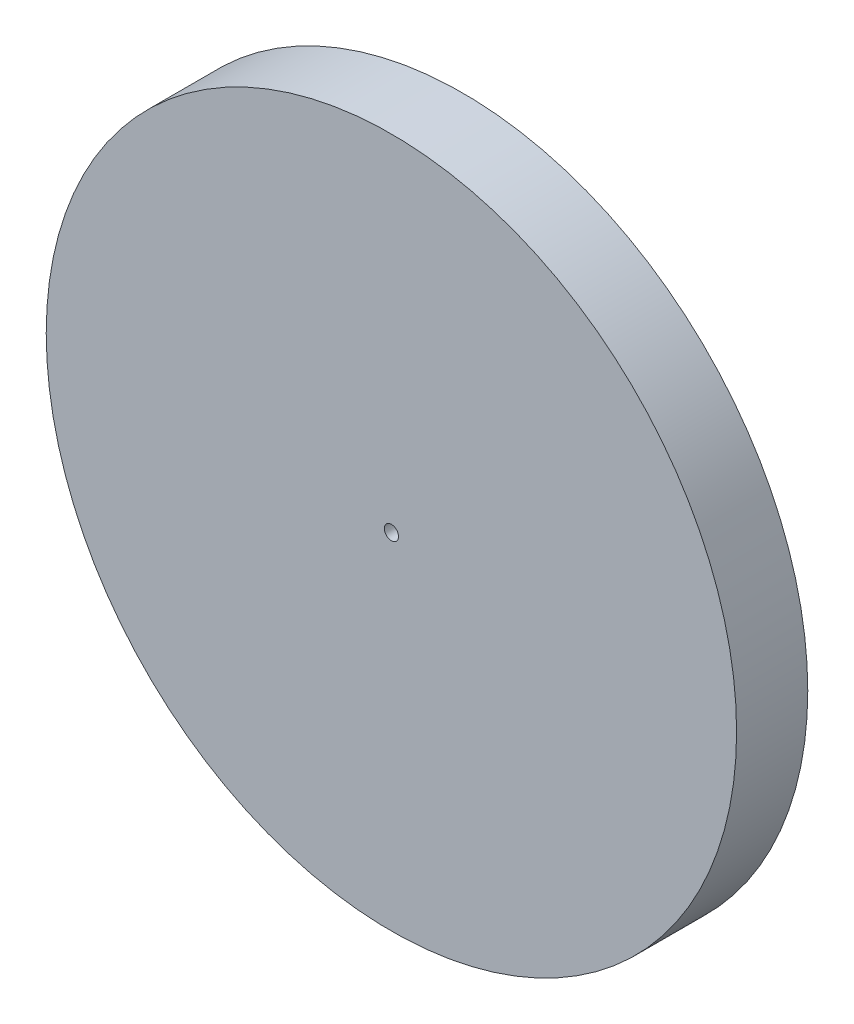
SolidWorks part; units mm, degrees
ref_plane "Front Plane" through (0, 0, 0) normal (0, 0, 1) x (1, 0, 0)
ref_plane "Top Plane" through (0, 0, 0) normal (0, 1, 0) x (1, 0, 0)
ref_plane "Right Plane" through (0, 0, 0) normal (1, 0, 0) x (0, 0, -1)
sketch "Sketch1" plane through (0, 0, 0) normal (0, 0, 1) x (1, 0, 0)
  circle A0 centre (0, 0) radius 48.5
  circle A1 centre (0, 0) radius 1
  dimension "D1" = 97
  dimension "D2" = 2
extrude "Boss-Extrude1" add sketch "Sketch1" along normal blind 10
